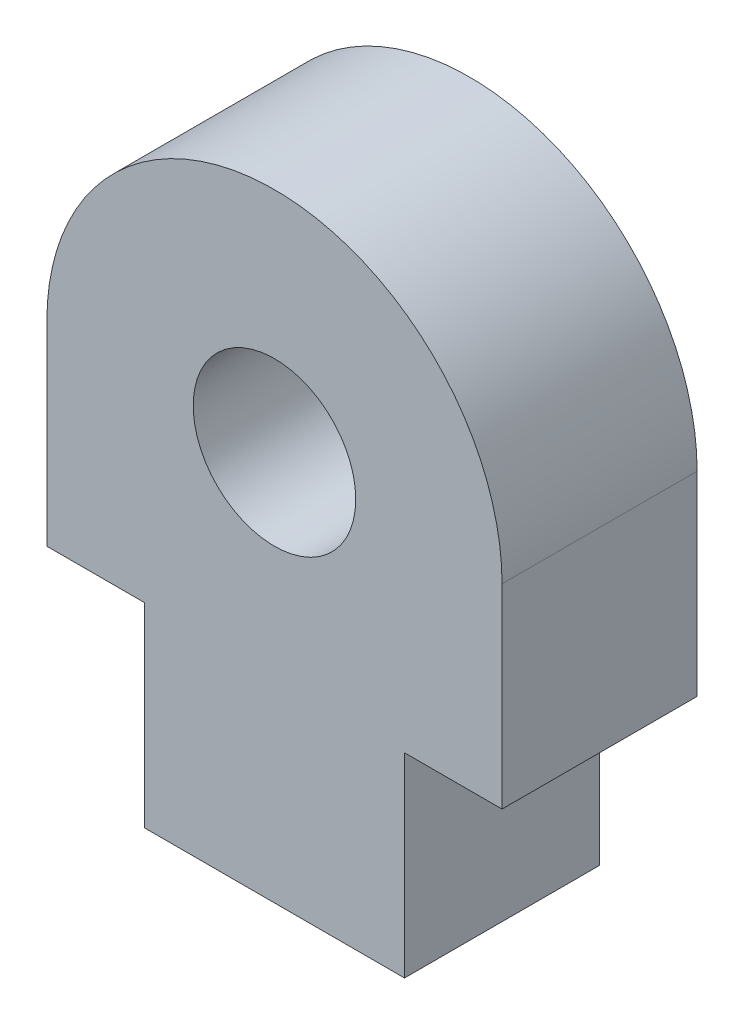
SolidWorks part; units mm, degrees
ref_plane "Front Plane" through (0, 0, 0) normal (0, 0, 1) x (1, 0, 0)
ref_plane "Top Plane" through (0, 0, 0) normal (0, 1, 0) x (1, 0, 0)
ref_plane "Right Plane" through (0, 0, 0) normal (1, 0, 0) x (0, 0, -1)
sketch "Sketch1" plane through (0, 0, 0) normal (0, 0, 1) x (1, 0, 0)
  line L0 (-3.5, 0) -> (-3.5, -3)
  line L1 (-3.5, -3) -> (-2, -3)
  line L2 (-2, -3) -> (-2, -6)
  line L3 (-2, -6) -> (2, -6)
  line L4 (2, -6) -> (2, -3)
  line L5 (2, -3) -> (3.5, -3)
  line L6 (3.5, -3) -> (3.5, 0)
  arc A0 (3.5, 0) -> (-3.5, 0) centre (0, 0) ccw
  circle A1 centre (0, 0) radius 1.25
  dimension "D1" = 2.5
  dimension "10" = 7
  dimension "D2" = 0
  dimension "D3" = 4
  dimension "D4" = 3
  dimension "D5" = 1.5
  dimension "D6" = 3
extrude "Boss-Extrude1" add sketch "Sketch1" along normal blind 3
